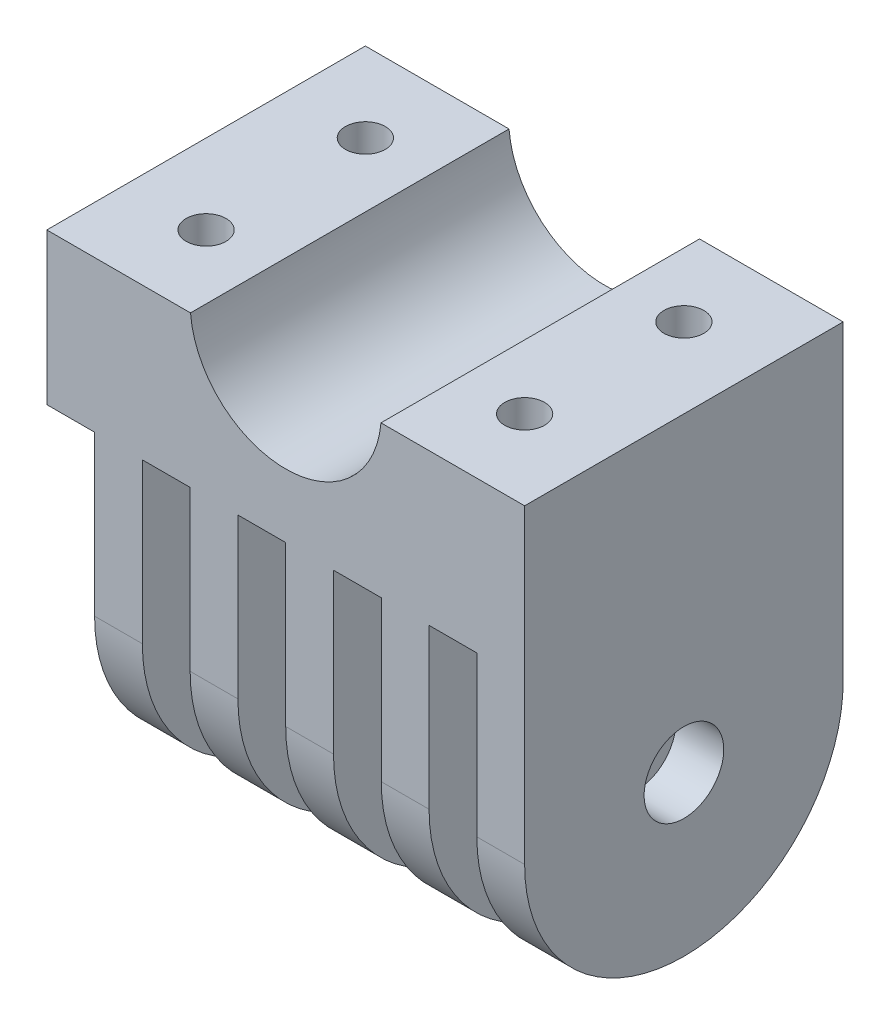
SolidWorks part; units mm, degrees
ref_plane "Plan de face" through (0, 0, 0) normal (0, 0, 1) x (1, 0, 0)
ref_plane "Plan de dessus" through (0, 0, 0) normal (0, 1, 0) x (1, 0, 0)
ref_plane "Plan de droite" through (0, 0, 0) normal (1, 0, 0) x (0, 0, -1)
sketch "Esquisse1" plane through (0, 0, 0) normal (0, 0, 1) x (1, 0, 0)
  line L0 (-15, -0.5) -> (-15, -10)
  line L1 (-15, -0.5) -> (-5.9791, -0.5)
  line L2 (14.4903, -0.5) -> (56.7257, -0.5) construction
  line L3 (15, -0.5) -> (15, -30)
  line L4 (5.9791, -0.5) -> (15, -0.5)
  line L5 (-15, -10) -> (-12, -10)
  line L6 (-12, -10) -> (-12, -30)
  line L7 (-12, -30) -> (-9, -30)
  line L8 (-9, -30) -> (-9, -10)
  line L9 (-9, -10) -> (-6, -10)
  line L10 (-6, -10) -> (-6, -30)
  line L11 (-6, -30) -> (-3, -30)
  line L12 (-3, -30) -> (-3, -10)
  line L13 (-3, -10) -> (0, -10)
  line L14 (0, -10) -> (0, -30)
  line L15 (0, -30) -> (3, -30)
  line L16 (3, -30) -> (3, -10)
  line L17 (3, -10) -> (6, -10)
  line L18 (6, -10) -> (6, -30)
  line L19 (6, -30) -> (9, -30)
  line L20 (9, -30) -> (9, -10)
  line L21 (9, -10) -> (12, -10)
  line L22 (12, -10) -> (12, -30)
  line L23 (12, -30) -> (15, -30)
  arc A0 (-5.9791, -0.5) -> (5.9791, -0.5) centre (0, 0) ccw
  dimension "D6" = 6
  dimension "D1" = 0.5
  dimension "D2" = 9.5
  dimension "D3" = 29.5
  dimension "D4" = 30
  dimension "D5" = 15
  dimension "D7" = 3
  dimension "D8" = 3
  dimension "D9" = 3
  dimension "D10" = 3
  dimension "D11" = 3
  dimension "D12" = 3
  dimension "D13" = 3
  dimension "D14" = 3
  dimension "D15" = 3
  dimension "D16" = 20
  dimension "D17" = 20
  dimension "D18" = 20
  dimension "D19" = 20
  dimension "D20" = 20
  dimension "D21" = 20
  dimension "D22" = 20
  dimension "D23" = 20
extrude "Boss.-Extru.1" add sketch "Esquisse1" along normal blind 20
sketch "Esquisse2" plane through (0, -0.5, 0) normal (0, 1, 0) x (1, 0, 0)
  line L0 (-15, -20) -> (-15, 0) construction
  line L1 (-5.9791, 0) -> (-15, 0) construction
  line L2 (-5.9791, -20) -> (-15, -20) construction
  line L3 (15, 0) -> (5.9791, 0) construction
  line L4 (15, -20) -> (15, 0) construction
  line L5 (15, -20) -> (5.9791, -20) construction
  circle A0 centre (-10, -5) radius 1.25
  circle A1 centre (-10, -15) radius 1.25
  circle A2 centre (10, -5) radius 1.25
  circle A3 centre (10, -15) radius 1.25
  dimension "D1" = 2.5
  dimension "D2" = 2.5
  dimension "D3" = 2.5
  dimension "D4" = 2.5
  dimension "D5" = 5
  dimension "D6" = 5
  dimension "D7" = 5
  dimension "D8" = 5
  dimension "D9" = 5
  dimension "D10" = 5
  dimension "D11" = 5
  dimension "D12" = 5
extrude "Enlèv. mat.-Extru.1" cut sketch "Esquisse2" against normal blind 8
fillet "Congé1" radius 10 10 edges at (-10.5, -30, 0) (-4.5, -30, 0) (1.5, -30, 0) (7.5, -30, 0) (13.5, -30, 0) (13.5, -30, 20) (7.5, -30, 20) (1.5, -30, 20) (-4.5, -30, 20) (-10.5, -30, 20)
sketch "Esquisse3" plane through (15, 0, 0) normal (1, 0, 0) x (0, 0, -1)
  line L0 (-20, -20) -> (-20, -0.5) construction
  circle A0 centre (-10, -20) radius 2.5
  arc A1 (-20, -20) -> (-10, -30) centre (-10, -20) ccw construction
  dimension "D1" = 5
  dimension "D2" = 0
  dimension "D3" = 10
extrude "Enlèv. mat.-Extru.2" cut sketch "Esquisse3" against normal blind 30
